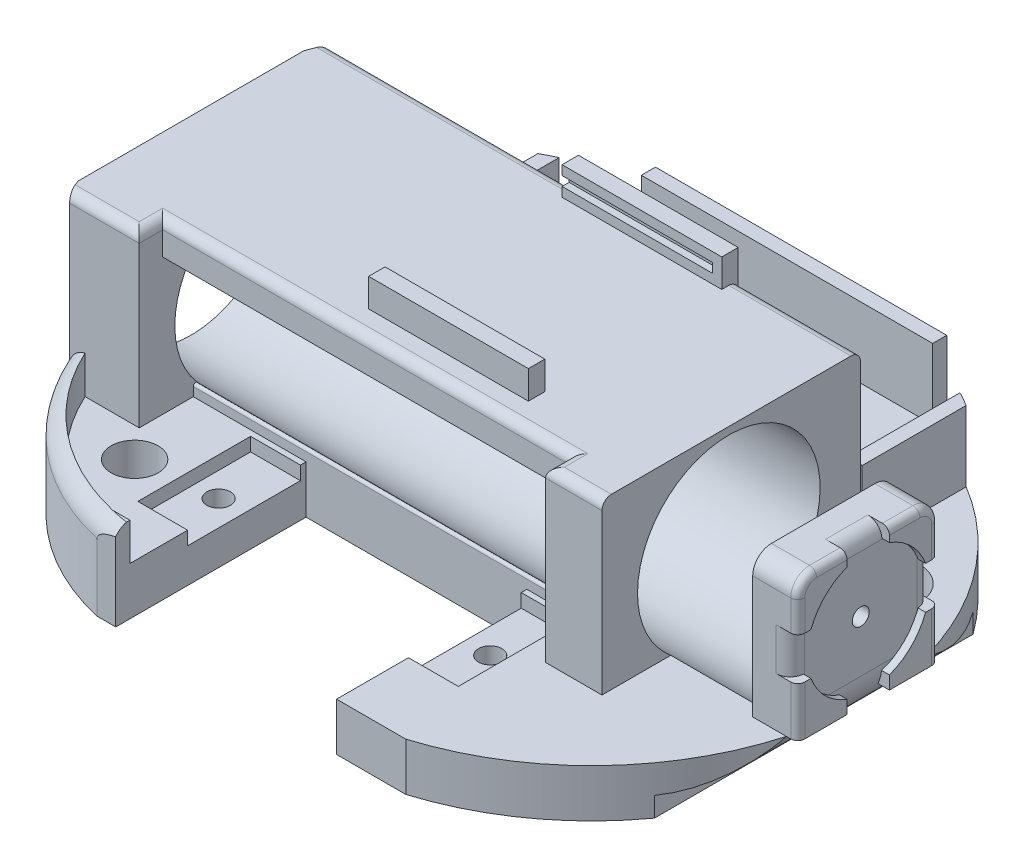
SolidWorks part; units mm, degrees
note: '?' marks a value the reader was unsure of. The reader was unsure of these and kept them because the rebuilt part matched: shared geometry of "Sketch3<7>".
ref_plane "Front Plane" through (0, 0, 0) normal (0, 0, 1) x (1, 0, 0)
ref_plane "Top Plane" through (0, 0, 0) normal (0, 1, 0) x (1, 0, 0)
ref_plane "Right Plane" through (0, 0, 0) normal (1, 0, 0) x (0, 0, -1)
sketch "Sketch1" plane through (0, 0, 0) normal (0, 1, 0) x (1, 0, 0)
  line L1 (-35.64, 28) -> (35.64, 28)
  line L2 (-35.64, 28) -> (-35.64, -28)
  line L3 (-35.64, -28) -> (35.64, -28)
  line L4 (35.64, 28) -> (35.64, -28)
  point P4 (0, 28)
  point P6 (-35.64, 0)
  dimension "D1" = 71.28
  dimension "D2" = 56
extrude "Boss-Extrude1" add sketch "Sketch1" along normal blind 3
sketch "Sketch2" plane through (0, 3, 0) normal (0, 1, 0) x (1, 0, 0)
  line L0 (35.64, -28) -> (35.64, 28) construction
  line L1 (35.64, 7.5) -> (31.64, 7.5)
  line L2 (35.64, 7.5) -> (35.64, -7.5)
  line L3 (35.64, -7.5) -> (31.64, -7.5)
  line L4 (31.64, 7.5) -> (31.64, -7.5)
  point P6 (35.64, 0)
  point P7 (35.64, 0)
  dimension "D1" = 15
  dimension "D2" = 4
extrude "Boss-Extrude2" add sketch "Sketch2" along normal blind 15
sketch "Sketch3" plane through (35.64, 0, 0) normal (1, 0, 0) x (0, 0, -1)
  line L0 (2.25, 4.4018) -> (2.25, 3)
  line L1 (6.0982, 12.75) -> (7.5, 12.75)
  line L2 (7.5, 18) -> (7.5, 3) construction
  line L3 (7.5, 12.75) -> (7.5, 8.25)
  line L4 (7.5, 8.25) -> (6.0982, 8.25)
  line L5 (7.5, 3) -> (28, 3) construction
  line L6 (-7.5, 18) -> (7.5, 18) construction
  line L7 (2.25, 3) -> (-2.25, 3)
  line L8 (-2.25, 3) -> (-2.25, 4.4018)
  line L9 (-6.0982, 8.25) -> (-7.5, 8.25)
  line L10 (-7.5, 8.25) -> (-7.5, 12.75)
  line L11 (-7.5, 12.75) -> (-6.0982, 12.75)
  line L12 (-2.25, 16.5982) -> (-2.25, 18)
  line L13 (-2.25, 18) -> (2.25, 18)
  line L14 (2.25, 18) -> (2.25, 16.5982)
  line L15 (-7.5, 3) -> (7.5, 3)
  circle A0 centre (0, 10.5) radius 6.5
  circle A1 centre (0, 10.5) radius 0.9
  point P16 (0, 18)
  point P18 (7.5, 10.5)
  point P29 (0, 10.5)
  line M4 (7.5, 3) -> (7.5, 18)
  line M5 (7.5, 18) -> (-7.5, 18)
  line M6 (-7.5, 18) -> (-7.5, 3)
  dimension "D2" = 13
  dimension "D5" = 1.8
  dimension "D1" = 7.5
  dimension "D3" = 4.5
  dimension "D4" = 4
extrude "Boss-Extrude4" add sketch "Sketch3" along normal blind 0.8 contours A0 L12 L11 M5 M6 | A0 L1 L14 M4 M5 | A0 L0 L15 L4 M4 | A0 L9 L15 L8 M6
fillet "Fillet2" radius 5 1 edges at (35.64, 0, 0)
fillet "Fillet3" radius 1.5 3 edges at (35.64, 10.5, 7.5) (35.64, 18, 0) (35.64, 10.5, -7.5)
fillet "Fillet4" radius 2 2 edges at (34.04, 18, -7.5) (34.04, 18, 7.5)
extrude "Cut-Extrude1" cut sketch "Sketch3<7>" against normal up to surface (4 mm away) contours A1 up to face at (31.64, 12.4714, 0)
sketch "Sketch3<7>" plane through (35.64, 0, 0) normal (1, 0, 0) x (0, 0, -1) same geometry as "Sketch3"
sketch "Sketch4" plane through (0, 3, 0) normal (0, 1, 0) x (1, 0, 0)
  line L0 (35.2226, 28) -> (-35.64, 28) construction
  line L1 (-35.64, -28) -> (35.2226, -28) construction
  line L2 (35.2226, -28) -> (35.2226, -7.5) construction
  line L3 (35.2226, 7.5) -> (35.2226, 28) construction
  arc A0 (35.2226, 7.5) -> (15.2226, 28) centre (6.3534, -0.659) ccw
  arc A1 (35.2226, -7.5) -> (15.2226, -28) centre (6.3534, 0.659) cw
  line M4 (35.2226, 7.5) -> (35.2226, 28)
  line M5 (35.2226, 28) -> (-35.64, 28)
  line M7 (-35.64, -28) -> (35.2226, -28)
  line M8 (35.2226, -28) -> (35.2226, -7.5)
  dimension "D2" = 30
  dimension "D3" = 30
  dimension "D1" = 20
  dimension "D4" = 20
extrude "Cut-Extrude2" cut sketch "Sketch4" against normal blind 10 contours A1 M8 M7 | A0 M4 M5
sketch "Sketch8" plane through (0, 3, 0) normal (0, 1, 0) x (1, 0, 0)
  line L0 (-35.64, 28) -> (-35.64, -28) construction
  line L1 (-35.64, -11) -> (21.6, -11)
  line L2 (-35.64, -11) -> (-35.64, 11)
  line L3 (-35.64, 11) -> (21.6, 11)
  line L4 (21.6, -11) -> (21.6, 11)
  point P6 (-35.64, 0)
  point P7 (-35.64, 0)
  dimension "D1" = 57.24
  dimension "D2" = 22
extrude "Boss-Extrude5" add sketch "Sketch8" along normal blind 18
sketch "Sketch9" plane through (-35.64, 0, 0) normal (-1, 0, 0) x (0, 0, 1)
  line L0 (-28, 0) -> (28, 0) construction
  circle A0 centre (0, 10.5) radius 9.715
  point P5 (0, 0)
  dimension "D2" = 19.43
  dimension "D1" = 10.5
extrude "Cut-Extrude3" cut sketch "Sketch9" against normal up to surface (67.28 mm away) up to face at (31.64, 10.5, -0.9)
sketch "Sketch21" plane through (0, 0, 0) normal (0, -1, 0) x (1, 0, 0)
  line L0 (15.2226, -28) -> (-35.64, -28) construction
  line L1 (-35.64, -28) -> (-35.64, 28) construction
  line L2 (-35.64, 28) -> (15.2226, 28) construction
  arc A0 (-17.64, -28) -> (-35.64, -12) centre (-12.0845, -3.6251) cw
  arc A1 (-17.64, 28) -> (-35.64, 12) centre (-12.0845, 3.6251) ccw
  line M22 (15.2226, 28) -> (-35.64, 28)
  line M23 (-35.64, 28) -> (-35.64, -28)
  line M24 (-35.64, -28) -> (15.2226, -28)
  dimension "D3" = 25
  dimension "D6" = 25
  dimension "D1" = 16
  dimension "D2" = 18
  dimension "D4" = 16
  dimension "D5" = 18
extrude "Cut-Extrude8" cut sketch "Sketch21" against normal through all contours A0 M24 M23 | A1 M22 M23
sketch "Sketch25" plane through (0, 0, 11) normal (0, 0, 1) x (1, 0, 0)
  line L0 (-35.64, 21) -> (-35.64, 3) construction
  line L1 (-27.64, 15.5) -> (15.6, 15.5)
  line L2 (-27.64, 15.5) -> (-27.64, 9)
  line L3 (-27.64, 9) -> (15.6, 9)
  line L4 (15.6, 15.5) -> (15.6, 9)
  line L5 (21.6, 21) -> (21.6, 3) construction
  line L6 (-35.64, 3) -> (21.6, 3) construction
  dimension "D1" = 8
  dimension "D2" = 6
  dimension "D3" = 6.5
  dimension "D4" = 6
extrude "Cut-Extrude10" cut sketch "Sketch25" against normal up to next
sketch "Sketch22" plane through (0, 3, 0) normal (0, 1, 0) x (1, 0, 0)
  line L0 (-35.64, -11) -> (-35.64, -12) construction
  line L1 (-15.64, -7.75) -> (7.86, -7.75)
  line L2 (-15.64, -7.75) -> (-15.64, -28)
  line L3 (-15.64, -28) -> (7.86, -28)
  line L4 (7.86, -7.75) -> (7.86, -28)
  line L5 (-17.64, -28) -> (15.2226, -28) construction
  point P6 (-35.64, -11.5)
  dimension "D1" = 20
  dimension "D2" = 23.5
  dimension "D3" = 20.25
extrude "Cut-Extrude9" cut sketch "Sketch22" against normal through all and the other way up to next contours L1 L4 L3 L2
sketch "Sketch33" plane through (0, 0, 0) normal (0, -1, 0) x (1, 0, 0)
  line L0 (-15.64, 7.75) -> (-15.64, 28) construction
  line L1 (-15.64, 25.75) -> (-21.64, 25.75)
  line L2 (-15.64, 25.75) -> (-15.64, 3.75)
  line L3 (-15.64, 3.75) -> (-21.64, 3.75)
  line L4 (-21.64, 25.75) -> (-21.64, 3.75)
  line L5 (7.86, 7.75) -> (7.86, 28) construction
  line L6 (7.86, 25.75) -> (13.86, 25.75)
  line L7 (7.86, 25.75) -> (7.86, 3.75)
  line L8 (7.86, 3.75) -> (13.86, 3.75)
  line L9 (13.86, 25.75) -> (13.86, 3.75)
  line L11 (-15.64, 7.75) -> (7.86, 7.75) construction
  dimension "D1" = 4
  dimension "D2" = 18
  dimension "D3" = 6
extrude "Boss-Extrude13" add sketch "Sketch33" along normal blind 0.5
sketch "Sketch47" plane through (0, 9, 0) normal (0, 1, 0) x (1, 0, 0)
  line L0 (-15.64, -11) -> (-15.64, -9.5985) construction
  line L1 (-27.64, -9.5985) -> (-27.64, -11) construction
  line L2 (-27.64, -11) -> (-15.64, -11) construction
  line L4 (7.86, -7.75) -> (-15.64, -7.75) construction
  line L8 (-15.64, -11) -> (-15.64, -7.75)
  line L9 (7.86, -9.5985) -> (7.86, -11)
  line L10 (7.86, -11) -> (15.6, -11)
  line L11 (15.6, -11) -> (15.6, -9.5985)
  line L12 (15.6, -9.5985) -> (7.86, -9.5985)
  line L13 (-15.64, -7.75) -> (-27.64, -7.75)
  line L14 (-27.64, -7.75) -> (-27.64, -11)
  line L15 (-27.64, -11) -> (-15.64, -11)
  line L17 (7.86, -7.75) -> (7.86, -11)
  line L18 (7.86, -11) -> (15.6, -11)
  line L19 (15.6, -11) -> (15.6, -7.75)
  line L20 (15.6, -7.75) -> (7.86, -7.75)
  dimension "D1" = 0
extrude "Cut-Extrude19" cut sketch "Sketch47" against normal up to surface (6 mm away) up to face at (-24.4507, 3, 18.4621)
fillet "Fillet8" radius 0.25 1 edges at (-6.02, 4.6418, 7.75)
sketch "Sketch26" plane through (0, 3, 0) normal (0, 1, 0) x (1, 0, 0)
  line L0 (-15.64, -7.75) -> (-15.64, -28) construction
  line L1 (7.86, -8.35) -> (13.16, -8.35)
  line L2 (7.86, -8.35) -> (7.86, -20.35)
  line L3 (7.86, -20.35) -> (13.16, -20.35)
  line L4 (13.16, -8.35) -> (13.16, -20.35)
  line L5 (-15.64, -8.35) -> (-20.94, -8.35)
  line L6 (-15.64, -8.35) -> (-15.64, -20.35)
  line L7 (-15.64, -20.35) -> (-20.94, -20.35)
  line L8 (-20.94, -8.35) -> (-20.94, -20.35)
  line L10 (7.86, -7.75) -> (7.86, -28) construction
  line L11 (-27.64, -7.75) -> (-15.64, -7.75) construction
  dimension "D1" = 0.6
  dimension "D2" = 12
  dimension "D4" = 5.3
extrude "Cut-Extrude11" cut sketch "Sketch26" against normal blind 1.44
sketch "Sketch27" plane through (0, 1.56, 0) normal (0, 1, 0) x (1, 0, 0)
  line L0 (-15.64, -20.35) -> (-15.64, -8.35) construction
  line L1 (7.86, -8.35) -> (7.86, -20.35) construction
  line L2 (-18.34, -14.35) -> (-15.64, -14.35) construction
  line L3 (-15.64, -20.35) -> (-15.64, -8.35) construction
  line L4 (10.56, -14.35) -> (7.86, -14.35) construction
  line L5 (7.86, -8.35) -> (7.86, -20.35) construction
  circle A0 centre (-18.34, -14.35) radius 1.25
  circle A1 centre (10.56, -14.35) radius 1.25
  point P7 (-15.64, -14.35)
  point P11 (7.86, -14.35)
  dimension "D1" = 2.5
  dimension "D3" = 28.9
extrude "Cut-Extrude12" cut sketch "Sketch27" against normal through all contours A0 | A1
sketch "Sketch30" [suppressed] plane through (0, 21, 0) normal (0, 1, 0) x (1, 0, 0)
  line L0 (-35.64, 11) -> (-35.64, -11) construction
  line L1 (-30.64, 2.5) -> (-2.64, 2.5)
  line L2 (-30.64, 2.5) -> (-30.64, -2.5)
  line L3 (-30.64, -2.5) -> (-2.64, -2.5)
  line L4 (-2.64, 2.5) -> (-2.64, -2.5)
  line L5 (-30.64, 2.5) -> (-2.64, -2.5) construction
  line L6 (-30.64, -2.5) -> (-2.64, 2.5) construction
  point P0 (-16.64, 0)
  dimension "D1" = 28
  dimension "D2" = 5
  dimension "D3" = 5
sketch "Sketch35" plane through (0, 3, 0) normal (0, 1, 0) x (1, 0, 0)
  line L0 (-21.64, 14) -> (21.6, 14)
  line L1 (21.6, 14) -> (21.6, 11)
  line L2 (21.6, 11) -> (-35.64, 11) construction
  line L3 (-21.64, 14) -> (-21.64, 11)
  line L6 (-35.64, 12) -> (-35.64, 11) construction
  line L15 (-35.64, 12) -> (-35.64, 11)
  line L16 (-35.64, 11) -> (21.6, 11)
  line L17 (21.6, 11) -> (21.6, 6.175)
  line L18 (21.6, 6.175) -> (31.64, 6.175)
  line L19 (31.64, 6.175) -> (31.64, 7.5)
  line L20 (31.64, 7.5) -> (35.2226, 7.5)
  line L21 (15.2226, 28) -> (-17.64, 28)
  line L23 (-21.64, 11) -> (21.6, 11)
  arc A2 (35.2226, 7.5) -> (15.2226, 28) centre (6.3534, -0.659) ccw
  arc A3 (-17.64, 28) -> (-35.64, 12) centre (-12.0845, 3.6251) ccw
  point P12 (-35.64, 11.5)
  dimension "D1" = 3
  dimension "D3" = 14
  dimension "D4" = 0
extrude "Boss-Extrude15" add sketch "Sketch35" along normal up to surface (18 mm away) up to face at (-7.02, 21, 0)
ref_plane "Plane1" through (0, 0, -9.715) normal (0, 0, 1) x (-1, 0, 0)
sketch "Sketch31" plane through (0, 0, -9.715) normal (0, 0, 1) x (-1, 0, 0)
  line L0 (35.64, -20.215) -> (35.64, -0.785) construction
  circle A0 centre (29.64, -10.5) radius 1.591
  point P4 (35.64, -10.5)
  dimension "D2" = 3.182
  dimension "D1" = 6
extrude "Cut-Extrude14" cut sketch "Sketch31" against normal up to next (1.285 mm away) and the other way up to next contours A0
ref_point "Point1" parameters "D1"=0
ref_plane "Plane2" through (0, 0, -11) normal (0, 0, 1) x (1, 0, 0)
sketch "Sketch43" plane through (0, 3, 0) normal (0, 1, 0) x (1, 0, 0)
  line L0 (21.6, 14) -> (-21.64, 14) construction
  line L1 (-21.64, 11) -> (-35.64, 11)
  line L2 (-21.64, 11) -> (-21.64, 14)
  line L3 (-21.64, 14) -> (-35.64, 14)
  line L4 (-35.64, 11) -> (-35.64, 14)
  line L5 (-35.64, 12) -> (-35.64, 11) construction
extrude "Boss-Extrude22" add sketch "Sketch43" along normal up to surface (18 mm away) up to face at (-11.8933, 21, -4.6667)
sketch "Sketch32" plane through (0, 0, -11) normal (0, 0, 1) x (1, 0, 0)
  circle A0 centre (-29.64, 10.5) radius 1.591 construction
  circle A1 centre (-29.64, 10.5) radius 1.591
extrude "Cut-Extrude15" cut sketch "Sketch32" against normal up to next and the other way blind 0.25
ref_point "Point2"
ref_axis "Axis2" through (31.64, 10.5, 0) along (-1, 0, 0)?
sketch "Sketch34" plane through (0, -0.5, 0) normal (0, -1, 0) x (1, 0, 0)
  line L0 (7.86, 25.75) -> (7.86, 3.75) construction
  line L1 (7.86, 3.75) -> (13.86, 3.75) construction
  line L2 (13.86, 3.75) -> (13.86, 25.75) construction
  line L3 (13.86, 25.75) -> (7.86, 25.75) construction
  line L4 (-15.64, 3.75) -> (-15.64, 25.75) construction
  line L5 (-15.64, 25.75) -> (-21.64, 25.75) construction
  line L7 (-21.64, 3.75) -> (-15.64, 3.75) construction
  line L8 (7.86, 25.75) -> (7.86, 3.75)
  line L9 (7.86, 3.75) -> (13.86, 3.75)
  line L10 (13.86, 3.75) -> (13.86, 25.75)
  line L11 (13.86, 25.75) -> (7.86, 25.75)
  line L12 (-15.64, 3.75) -> (-15.64, 25.75)
  line L13 (-15.64, 25.75) -> (-21.64, 25.75)
  line L14 (-21.64, 25.75) -> (-21.64, 3.75) construction
  line L15 (-21.64, 3.75) -> (-15.64, 3.75)
  line L16 (-21.64, 25.75) -> (-21.64, 3.75)
  line L17 (-16.355, 13.204) -> (-18.34, 12.0579)
  line L18 (-18.34, 12.0579) -> (-20.325, 13.204)
  line L19 (-20.325, 13.204) -> (-20.325, 15.496)
  line L20 (-20.325, 15.496) -> (-18.34, 16.6421)
  line L21 (-18.34, 16.6421) -> (-16.355, 15.496)
  line L22 (-16.355, 15.496) -> (-16.355, 13.204)
  line L23 (8.575, 13.204) -> (10.56, 12.0579)
  line L24 (10.56, 12.0579) -> (12.545, 13.204)
  line L25 (12.545, 13.204) -> (12.545, 15.496)
  line L26 (12.545, 15.496) -> (10.56, 16.6421)
  line L27 (10.56, 16.6421) -> (8.575, 15.496)
  line L28 (8.575, 15.496) -> (8.575, 13.204)
  circle A0 centre (10.56, 14.35) radius 1.25 construction
  circle A1 centre (-18.34, 14.35) radius 1.25 construction
  circle A2 centre (10.56, 14.35) radius 1.25 construction
  circle A3 centre (-18.34, 14.35) radius 1.25 construction
  circle A4 centre (-18.34, 14.35) radius 1.985 construction
  circle A5 centre (10.56, 14.35) radius 1.985 construction
  dimension "D1" = 3.97
  dimension "D2" = 3.97
extrude "Boss-Extrude14" add sketch "Sketch34" along normal blind 1.6
ref_plane "Plane3" through (7.6, 0, 0) normal (1, 0, 0) x (0, 0, -1)
ref_point "Point3" [suppressed]
sketch "Sketch45" plane through (7.6, 0, 0) normal (1, 0, 0) x (0, 0, -1)
  line L0 (-6.58, 23) -> (-6.58, 24)
  line L1 (-8.33, 21) -> (-6.58, 21)
  line L2 (-8.33, 21) -> (-8.33, 24)
  line L3 (-8.33, 24) -> (-6.58, 24)
  line L4 (-6.58, 21) -> (-6.58, 22)
  line L5 (14, 21) -> (12.25, 21)
  line L6 (14, 21) -> (14, 24)
  line L7 (14, 24) -> (12.25, 24)
  line L8 (12.25, 21) -> (12.25, 22)
  line L9 (-6.58, 23) -> (-7.33, 23)
  line L10 (12.25, 23) -> (12.25, 24)
  line L11 (-6.58, 22) -> (-7.33, 22)
  line L12 (-7.33, 23) -> (-7.33, 22)
  line L13 (12.25, 23) -> (13, 23)
  line L15 (12.25, 22) -> (13, 22)
  line L16 (13, 23) -> (13, 22)
  dimension "D1" = 1.75
  dimension "D2" = 1.75
  dimension "D3" = 3
  dimension "D4" = 1
  dimension "D5" = 0.75
  dimension "D6" = 1
  dimension "D7" = 20.33
extrude "Boss-Extrude23" add sketch "Sketch45" against normal blind 16 contours L3 L0 L9 L12 L11 L4 L1 L2 | L6 L7 L10 L13 L16 L15 L8 L5
sketch "Sketch71" plane through (7.6, 0, 0) normal (1, 0, 0) x (0, 0, -1)
  line L1 (-8.33, 24) -> (-6.58, 24)
  line L2 (-8.33, 24) -> (-8.33, 21)
  line L3 (-8.33, 21) -> (-6.58, 21)
  line L4 (-6.58, 24) -> (-6.58, 21)
  line L5 (14, 24) -> (12.25, 24)
  line L6 (14, 24) -> (14, 21)
  line L7 (14, 21) -> (12.25, 21)
  line L8 (12.25, 24) -> (12.25, 21)
extrude "Boss-Extrude34" add sketch "Sketch71" along normal blind 1
ref_point "Point4"
ref_plane "Plane4" [suppressed] through (0, 0, 9.715) normal (0, 0, -1) x (-1, 0, 0)
sketch "Sketch48" plane through (0, 3, 0) normal (0, 1, 0) x (1, 0, 0)
  line L0 (-35.64, -11) -> (-35.64, -12) construction
  line L1 (15.6, -11) -> (21.6, -11)
  line L2 (15.6, -11) -> (15.6, -13.5)
  line L3 (15.6, -13.5) -> (21.6, -13.5)
  line L4 (21.6, -11) -> (21.6, -13.5)
  line L5 (-27.64, -11) -> (-35.64, -11)
  line L6 (-27.64, -11) -> (-27.64, -13.5)
  line L7 (-27.64, -13.5) -> (-35.64, -13.5)
  line L8 (-35.64, -11) -> (-35.64, -13.5)
  line L9 (21.6, -11) -> (21.6, -6.175) construction
  dimension "D1" = 2.5
extrude "Boss-Extrude25" add sketch "Sketch48" along normal up to surface (18 mm away) up to face at (0.1, 21, 7.455)
sketch "Sketch52" plane through (0, 0, 0) normal (0, -1, 0) x (1, 0, 0)
  line L2 (-21.64, 25.75) -> (-15.64, 25.75)
  line L3 (-15.64, 25.75) -> (-15.64, 28)
  line L4 (-21.64, 25.75) -> (-15.64, 25.75)
  line L5 (-15.64, 25.75) -> (-15.64, 28)
  line L20 (15.2226, 28) -> (7.86, 28)
  line L21 (15.2226, 28) -> (7.86, 28)
  line L22 (7.86, 3.75) -> (7.86, 7.75)
  line L23 (7.86, 3.75) -> (7.86, 7.75)
  line L24 (7.86, 7.75) -> (-15.64, 7.75)
  line L25 (7.86, 7.75) -> (-15.64, 7.75)
  line L26 (-35.64, 12) -> (-35.64, -12)
  line L27 (-35.64, 12) -> (-35.64, -12)
  line L28 (-17.64, -28) -> (15.2226, -28)
  line L29 (-17.64, -28) -> (15.2226, -28)
  line L30 (30.64, -16.9524) -> (30.64, 16.9524)
  line L31 (30.64, -16.9524) -> (30.64, 16.9524)
  line L32 (-15.64, 7.75) -> (-15.64, 3.75)
  line L33 (-15.64, 7.75) -> (-15.64, 3.75)
  line L34 (-15.64, 3.75) -> (-21.64, 3.75)
  line L35 (-15.64, 3.75) -> (-21.64, 3.75)
  line L36 (-21.64, 3.75) -> (-21.64, 25.75)
  line L37 (-21.64, 3.75) -> (-21.64, 25.75)
  line L38 (-15.64, 28) -> (-17.64, 28)
  line L39 (-15.64, 28) -> (-17.64, 28)
  line L40 (7.86, 28) -> (7.86, 25.75)
  line L41 (7.86, 28) -> (7.86, 25.75)
  line L42 (7.86, 25.75) -> (13.86, 25.75)
  line L43 (7.86, 25.75) -> (13.86, 25.75)
  line L44 (13.86, 25.75) -> (13.86, 3.75)
  line L45 (13.86, 25.75) -> (13.86, 3.75)
  line L46 (13.86, 3.75) -> (7.86, 3.75)
  line L47 (13.86, 3.75) -> (7.86, 3.75)
  arc A1 (-17.64, 28) -> (-35.64, 12) centre (-12.0845, 3.6251) ccw
  arc A2 (-17.64, 28) -> (-35.64, 12) centre (-12.0845, 3.6251) ccw
  arc A6 (-35.64, -12) -> (-17.64, -28) centre (-12.0845, -3.6251) ccw
  arc A7 (-35.64, -12) -> (-17.64, -28) centre (-12.0845, -3.6251) ccw
  arc A8 (15.2226, -28) -> (30.64, -16.9524) centre (6.3534, 0.659) ccw
  arc A9 (15.2226, -28) -> (30.64, -16.9524) centre (6.3534, 0.659) ccw
  arc A10 (30.64, 16.9524) -> (15.2226, 28) centre (6.3534, -0.659) ccw
  arc A11 (30.64, 16.9524) -> (15.2226, 28) centre (6.3534, -0.659) ccw
  dimension "D1" = 0
extrude "Cut-Extrude22" [suppressed] cut sketch "Sketch52" against normal through all
sketch "Sketch53" plane through (0, 3, 0) normal (0, -1, 0) x (1, 0, 0)
  line L2 (-35.64, 13.5) -> (-35.64, 12)
  line L3 (-35.0516, 13.5) -> (-35.64, 13.5)
  line L4 (-35.64, 13.5) -> (-35.64, 12)
  line L5 (-35.0516, 13.5) -> (-35.64, 13.5)
  line L6 (-35.64, -14) -> (-34.8301, -14)
  line L7 (-35.64, -12) -> (-35.64, -14)
  line L8 (-35.64, -14) -> (-34.8301, -14)
  line L9 (-35.64, -12) -> (-35.64, -14)
  arc A1 (-35.0516, 13.5) -> (-35.64, 12) centre (-12.0845, 3.6251) ccw
  arc A2 (-35.0516, 13.5) -> (-35.64, 12) centre (-12.0845, 3.6251) ccw
  arc A3 (-35.64, -12) -> (-34.8301, -14) centre (-12.0845, -3.6251) ccw
  arc A4 (-35.64, -12) -> (-34.8301, -14) centre (-12.0845, -3.6251) ccw
  dimension "D1" = 0
  dimension "D2" = 0
extrude "Cut-Extrude23" cut sketch "Sketch53" against normal through all
ref_axis "Axis3" through (31.64, 10.5, 0) along (-1, 0, 0)?
fillet "Fillet7" radius 1 5 edges at (-6.02, 21, 11) (15.6, 21, 12.25) (-27.64, 21, 12.25) (-31.3458, 21, 13.5) (18.6, 21, 13.5)
sketch "Sketch56" plane through (0, 0, -28) normal (0, 0, -1) x (-1, 0, 0)
  line L0 (-15.2226, 3) -> (17.64, 3) construction
  line L1 (-15.2226, 0) -> (17.64, 0) construction
  line L8 (-14.2913, 0) -> (16.7087, 0)
  line L9 (16.7087, 0) -> (16.7087, 3)
  line L10 (16.7087, 3) -> (-14.2913, 3)
  line L11 (-14.2913, 3) -> (-14.2913, 0)
  point P2 (1.2087, 3)
  point P7 (1.2087, 3)
  dimension "D1" = 31
  dimension "D2" = 0
extrude "Boss-Extrude29" add sketch "Sketch56" along normal blind 2.5 and the other way blind 1
sketch "Sketch57" plane through (0, 3, 0) normal (0, 1, 0) x (1, 0, 0)
  line L1 (14.2913, 30.5) -> (-16.7087, 30.5)
  line L2 (-24.2087, 14) -> (-24.2087, 25.4884)
  line L3 (14.2913, 29) -> (-16.7087, 29)
  line L4 (-22.7087, 14) -> (-22.7087, 26.2553)
  line L5 (21.6, 14) -> (-34.8301, 14) construction
  line L6 (20.2913, 14) -> (21.7913, 14)
  line L7 (21.7913, 14) -> (21.7913, 25.064)
  line L8 (-16.7087, 29) -> (-16.7087, 30.5)
  line L9 (20.2913, 14) -> (20.2913, 25.9067)
  line L10 (14.2913, 29) -> (14.2913, 30.5)
  line L11 (-22.7087, 14) -> (-24.2087, 14)
  line L12 (-16.7087, 30.5) -> (14.2913, 30.5) construction
  line L13 (14.2913, 30.5) -> (14.2913, 28) construction
  line L14 (20.2913, 19.9533) -> (-22.7087, 20.1276) construction
  arc A0 (35.2226, 7.5) -> (15.2226, 28) centre (6.3534, -0.659) ccw construction
  arc A1 (21.7913, 25.064) -> (20.2913, 25.9067) centre (6.3534, -0.659) ccw
  arc A2 (-17.64, 28) -> (-34.8301, 14) centre (-12.0845, 3.6251) ccw construction
  arc A3 (-22.7087, 26.2553) -> (-24.2087, 25.4884) centre (-12.0845, 3.6251) ccw
  point P4 (-1.2087, 20.0405)
  point P27 (-1.2087, 30.5)
  dimension "D2" = 1.5
  dimension "D1" = 1.5
  dimension "D3" = 1.5
  dimension "D4" = 0
  dimension "D5" = 43
extrude "Boss-Extrude30" add sketch "Sketch57" along normal blind 7.5 and the other way up to surface
fillet "Fillet12" radius 1 4 edges at (15.1, 21, -14) (-21.615, 21, -14) (-29.5194, 3, -14) (-1.2087, 3, -14)
fillet "Fillet15" radius 0.75 8 edges at (36.44, 18, -3.875) (36.44, 17.4142, -6.9142) (36.44, 18, 3.875) (36.44, 17.4142, 6.9142) (36.44, 5.625, 7.5) (36.44, 5.625, -7.5) (36.44, 14.375, -7.5) (36.44, 14.375, 7.5)
sketch "Sketch61" plane through (0, 15.5, 0) normal (0, -1, 0) x (1, 0, 0)
  line L0 (15.6, 8.3295) -> (15.6, 11) construction
  line L1 (-27.64, 11) -> (15.6, 11)
  line L2 (-27.64, 11) -> (-27.64, 5.2198)
  line L3 (-27.64, 5.2198) -> (15.6, 5.2198)
  line L4 (15.6, 11) -> (15.6, 5.2198)
extrude "Cut-Extrude27" cut sketch "Sketch61" against normal blind 2
sketch "Sketch64" plane through (0, 0, 0) normal (0, -1, 0) x (1, 0, 0)
  line L20 (14.2913, -28) -> (15.2226, -28)
  line L21 (30.64, -16.9524) -> (30.64, 16.9524)
  line L22 (15.2226, 28) -> (7.86, 28)
  line L23 (7.86, 28) -> (7.86, 25.75)
  line L24 (7.86, 25.75) -> (13.86, 25.75)
  line L25 (13.86, 25.75) -> (13.86, 3.75)
  line L26 (13.86, 3.75) -> (7.86, 3.75)
  line L27 (7.86, 3.75) -> (7.86, 7.75)
  line L28 (7.86, 7.75) -> (-15.64, 7.75)
  line L29 (-15.64, 7.75) -> (-15.64, 3.75)
  line L30 (-15.64, 3.75) -> (-21.64, 3.75)
  line L31 (-21.64, 3.75) -> (-21.64, 25.75)
  line L32 (-21.64, 25.75) -> (-15.64, 25.75)
  line L33 (-15.64, 25.75) -> (-15.64, 28)
  line L34 (-15.64, 28) -> (-17.64, 28)
  line L35 (-35.64, 12) -> (-35.64, -12)
  line L36 (-17.64, -28) -> (-16.7087, -28)
  line L37 (-16.7087, -28) -> (-16.7087, -30.5)
  line L38 (-16.7087, -30.5) -> (14.2913, -30.5)
  line L39 (14.2913, -30.5) -> (14.2913, -28)
  line L40 (14.2913, -28) -> (15.2226, -28)
  line L41 (30.64, -16.9524) -> (30.64, 16.9524)
  line L42 (15.2226, 28) -> (7.86, 28)
  line L43 (7.86, 28) -> (7.86, 25.75)
  line L44 (7.86, 25.75) -> (13.86, 25.75)
  line L45 (13.86, 25.75) -> (13.86, 3.75)
  line L46 (13.86, 3.75) -> (7.86, 3.75)
  line L47 (7.86, 3.75) -> (7.86, 7.75)
  line L48 (7.86, 7.75) -> (-15.64, 7.75)
  line L49 (-15.64, 7.75) -> (-15.64, 3.75)
  line L50 (-15.64, 3.75) -> (-21.64, 3.75)
  line L51 (-21.64, 3.75) -> (-21.64, 25.75)
  line L52 (-21.64, 25.75) -> (-15.64, 25.75)
  line L53 (-15.64, 25.75) -> (-15.64, 28)
  line L54 (-15.64, 28) -> (-17.64, 28)
  line L55 (-35.64, 12) -> (-35.64, -12)
  line L56 (-17.64, -28) -> (-16.7087, -28)
  line L57 (-16.7087, -28) -> (-16.7087, -30.5)
  line L58 (-16.7087, -30.5) -> (14.2913, -30.5)
  line L59 (14.2913, -30.5) -> (14.2913, -28)
  arc A4 (15.2226, -28) -> (30.64, -16.9524) centre (6.3534, 0.659) ccw
  arc A5 (30.64, 16.9524) -> (15.2226, 28) centre (6.3534, -0.659) ccw
  arc A6 (-17.64, 28) -> (-35.64, 12) centre (-12.0845, 3.6251) ccw
  arc A7 (-35.64, -12) -> (-17.64, -28) centre (-12.0845, -3.6251) ccw
  arc A8 (15.2226, -28) -> (30.64, -16.9524) centre (6.3534, 0.659) ccw
  arc A9 (30.64, 16.9524) -> (15.2226, 28) centre (6.3534, -0.659) ccw
  arc A10 (-17.64, 28) -> (-35.64, 12) centre (-12.0845, 3.6251) ccw
  arc A11 (-35.64, -12) -> (-17.64, -28) centre (-12.0845, -3.6251) ccw
  dimension "D1" = 0
extrude "Boss-Extrude31" add sketch "Sketch64" along normal up to surface (2.1 mm away) up to face at (10.86, -2.1, 14.75)
sketch "Sketch65" plane through (0, -2.1, 0) normal (0, -1, 0) x (1, 0, 0)
  line L1 (-24.64, 0.75) -> (-6.71, 0.75)
  line L2 (-24.64, 0.75) -> (-24.64, -17.18)
  line L3 (-24.64, -17.18) -> (-6.71, -17.18)
  line L4 (-6.71, 0.75) -> (-6.71, -17.18)
  line L5 (6.29, -1.25) -> (19.14, -1.25)
  line L6 (6.29, -1.25) -> (6.29, -11.56)
  line L7 (6.29, -11.56) -> (19.14, -11.56)
  line L8 (19.14, -1.25) -> (19.14, -11.56)
  line L9 (7.86, 7.75) -> (-15.64, 7.75) construction
  line L10 (-35.64, 12) -> (-35.64, -12) construction
  dimension "D1" = 17.93
  dimension "D2" = 17.93
  dimension "D3" = 12.85
  dimension "D4" = 10.31
  dimension "D5" = 9
  dimension "D6" = 11
  dimension "D7" = 13
  dimension "D8" = 7
extrude "Cut-Extrude28" cut sketch "Sketch65" against normal blind 2.6
sketch "Sketch66" plane through (0, 3, 0) normal (0, 1, 0) x (1, 0, 0)
  circle A0 centre (26.4682, 11.9342) radius 3.5
  circle A1 centre (-24.9886, -16.6422) radius 2.5
  dimension "D1" = 7
  dimension "D2" = 5
extrude "Cut-Extrude29" cut sketch "Sketch66" against normal through all
sketch "Sketch67" plane through (0, 3, 0) normal (0, 1, 0) x (1, 0, 0)
  line L0 (-17.64, -28) -> (-15.64, -28) construction
  line L1 (-17.64, -28) -> (-15.64, -28)
  line L2 (-17.4686, -26.5) -> (-15.64, -26.5)
  line L3 (-35.0516, -13.5) -> (-33.4091, -13.5)
  line L4 (-35.0516, -13.5) -> (-27.64, -13.5) construction
  line L5 (-15.64, -28) -> (-15.64, -26.5)
  arc A0 (-35.0516, -13.5) -> (-17.64, -28) centre (-12.0845, -3.6251) ccw construction
  arc A1 (-35.0516, -13.5) -> (-17.64, -28) centre (-12.0845, -3.6251) ccw
  arc A2 (-33.4091, -13.5) -> (-17.4686, -26.5) centre (-12.0845, -3.6251) ccw
  arc A3 (-33.6736, -12.9075) -> (-17.4686, -26.5) centre (-12.0845, -3.6251) ccw construction
  dimension "D1" = 1.5
extrude "Boss-Extrude32" add sketch "Sketch67" along normal blind 4
fillet "Fillet16" radius 2 1 edges at (-28.0828, 7, 22.8358)
sketch "Sketch68" [suppressed] plane through (0, -2.1, 0) normal (0, -1, 0) x (1, 0, 0)
  line L0 (24.2185, -9.253) -> (15.7487, -16.36)
  line L1 (15.7487, -16.36) -> (2.5154, -16.36)
  line L2 (2.5154, -16.36) -> (2.5154, -13.36)
  line L3 (2.5154, -13.36) -> (-4.4846, -13.36)
  line L4 (-4.4846, -13.36) -> (-4.4846, -23.36)
  line L5 (-4.4846, -23.36) -> (18.2965, -23.36)
  line L6 (18.2965, -23.36) -> (28.718, -14.6153)
  line L7 (6.29, -11.56) -> (19.14, -11.56) construction
  line L8 (-21.5074, 6.75) -> (-22.5005, 16.886)
  line L9 (-21.5074, 6.75) -> (2.5154, 6.75)
  line L10 (2.5154, 6.75) -> (2.5154, -1.25)
  line L11 (2.5154, -1.25) -> (-4.4846, -1.25)
  line L12 (-4.4846, -1.25) -> (-4.4846, 1.75)
  line L13 (-4.4846, 1.75) -> (-26.0414, 1.75)
  line L14 (-26.0414, 1.75) -> (-27.4767, 16.3984)
  line L15 (7.86, 7.75) -> (-15.64, 7.75) construction
  circle A0 centre (26.4682, -11.9342) radius 3.5 construction
  circle A1 centre (26.4682, -11.9342) radius 3.5
  circle A2 centre (-24.9886, 16.6422) radius 2.5 construction
  circle A3 centre (-24.9886, 16.6422) radius 2.5
  dimension "D1" = 7
  dimension "D2" = 7
  dimension "D3" = 7
  dimension "D4" = 3
  dimension "D5" = 140
  dimension "D6" = 1.8
  dimension "D7" = 5
  dimension "D8" = 1
  dimension "D9" = 5
  dimension "D10" = 3
equation "\"D2@Sketch34\"= \"D1@Sketch34\""
equation "\"D1@Sketch57\"=\"D2@Sketch57\""
equation "\"D3@Sketch57\"=\"D2@Sketch57\""
equation "\"D3@Sketch4\"=\"D2@Sketch4\""
equation "\"D1@Sketch1\"=66.00mm*1.08"
equation "\"D1@Sketch8\"=1.08*53.00mm"
equation "\"D1@Sketch68\"=\"D2@Sketch68\""
equation "\"D3@Sketch68\"=\"D2@Sketch68\""
equation "\"D5@Sketch65\"=\"D8@Sketch65\"+2"
equation "\"D7@Sketch68\"=\"D9@Sketch68\""
